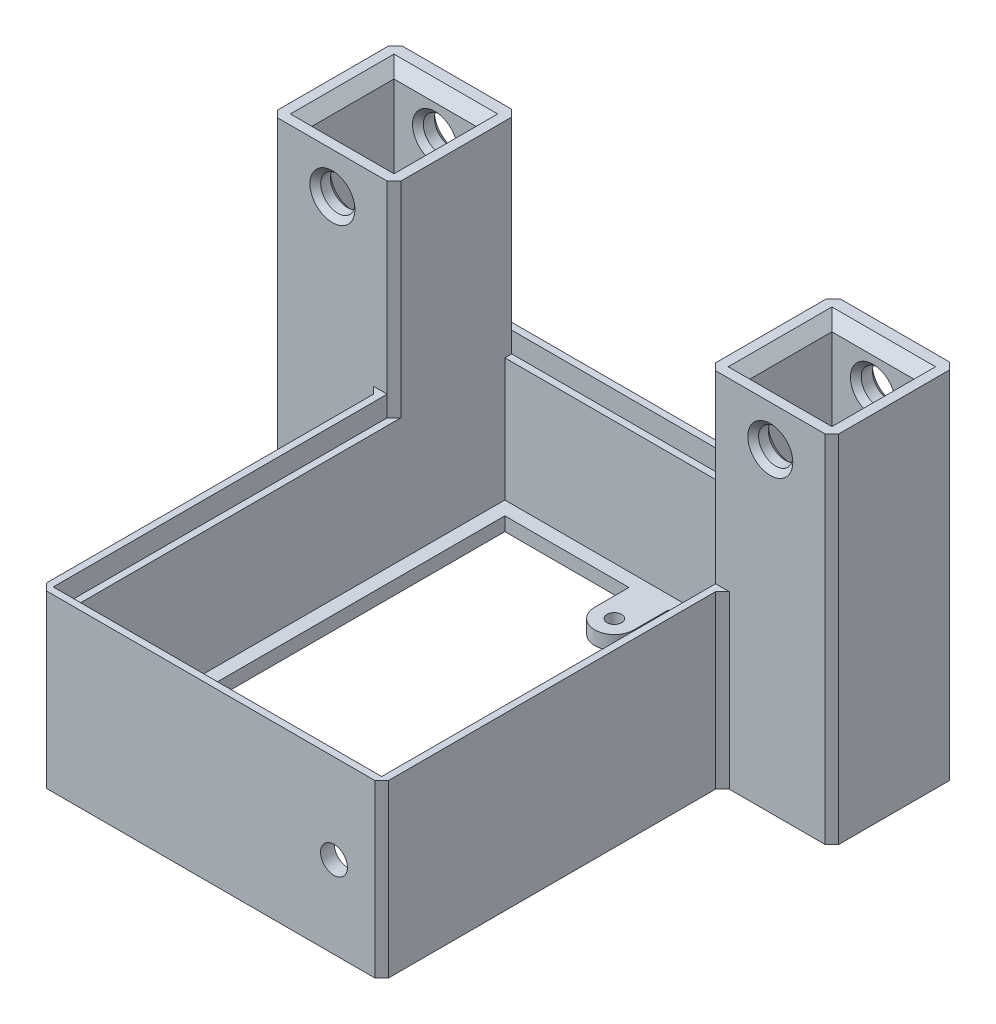
SolidWorks part; units mm, degrees
ref_plane "Front Plane" through (0, 0, 0) normal (0, 0, 1) x (1, 0, 0)
ref_plane "Top Plane" through (0, 0, 0) normal (0, 1, 0) x (1, 0, 0)
ref_plane "Right Plane" through (0, 0, 0) normal (1, 0, 0) x (0, 0, -1)
sketch "Sketch3" plane through (0, 0, 0) normal (0, 1, 0) x (-1, 0, 0)
  line L1 (0, 0) -> (63.5, 0)
  line L2 (0, 0) -> (0, 86.36)
  line L3 (0, 86.36) -> (63.5, 86.36)
  line L4 (63.5, 0) -> (63.5, 86.36)
  dimension "D1" = 86.36
  dimension "D2" = 63.5
extrude "Boss-Extrude2" add sketch "Sketch3" against normal blind 31.75
sketch "Sketch4" plane through (0, -31.75, 0) normal (0, -1, 0) x (1, 0, 0)
  line L1 (-2.54, 83.82) -> (-60.96, 83.82)
  line L2 (-2.54, 83.82) -> (-2.54, 2.54)
  line L3 (-2.54, 2.54) -> (-60.96, 2.54)
  line L4 (-60.96, 83.82) -> (-60.96, 2.54)
  line L8 (-63.5, 86.36) -> (0, 86.36) construction
  line L9 (0, 0) -> (-63.5, 0) construction
  line L10 (0, 86.36) -> (0, 0) construction
  line L11 (-63.5, 0) -> (-63.5, 86.36) construction
  dimension "D1" = 2.54
  dimension "D2" = 2.54
  dimension "D3" = 2.54
  dimension "D4" = 2.54
extrude "Cut-Extrude2" cut sketch "Sketch4" against normal offset from surface (27.94 mm away) 3.81 up to face at (-31.75, 0, 43.18)
sketch "Sketch5" plane through (-63.5, 0, 0) normal (1, 0, 0) x (0, 0, -1)
  line L0 (-86.36, -31.75) -> (-86.36, 0) construction
  line L5 (0, -31.75) -> (-86.36, -31.75) construction
  circle A0 centre (-76.327, -19.177) radius 5.715
  dimension "D1" = 11.43
  dimension "D2" = 6.858
  dimension "D3" = 4.318
extrude "Power Jack Hole" cut sketch "Sketch5" along normal up to next
sketch "Sketch6" plane through (-63.5, 0, 0) normal (-1, 0, 0) x (0, 0, 1)
  line L0 (46.54, 0) -> (46.54, 36.83)
  line L1 (46.54, 36.83) -> (0, 36.83)
  line L2 (0, 36.83) -> (0, 34.29)
  line L3 (0, 34.29) -> (44, 34.29)
  line L4 (44, 34.29) -> (44, 0)
  line L5 (0, 0) -> (86.36, 0) construction
  line L6 (44, 0) -> (46.54, 0)
  line L7 (0, -31.75) -> (0, 0) construction
  dimension "D1" = 44
  dimension "D2" = 34.29
  dimension "D3" = 2.54
  dimension "D4" = 2.54
extrude "Motor Mounting Shape" add sketch "Sketch6" against normal up to surface (63.5 mm away) up to face at (0, -15.875, 43.18)
sketch "Sketch8" plane through (0, 36.83, 0) normal (0, 1, 0) x (1, 0, 0)
  line L0 (-47.25, -38.77) -> (-16.25, -7.77) construction
  line L1 (-16.25, -38.77) -> (-47.25, -7.77) construction
  line L2 (-47.25, -38.77) -> (-47.25, -7.77) construction
  line L3 (-47.25, -7.77) -> (-16.25, -7.77) construction
  line L4 (-31.75, -46.54) -> (-31.75, 0) construction
  line L5 (0, -46.54) -> (-63.5, -46.54) construction
  line L6 (0, 0) -> (-63.5, 0) construction
  line L7 (-40.64, 0) -> (-22.86, 0)
  line L8 (-22.86, 0) -> (-22.86, -23.27)
  line L9 (-40.64, -23.27) -> (-40.64, 0)
  circle A1 centre (-47.25, -7.77) radius 1.6
  circle A2 centre (-16.25, -7.77) radius 1.6
  circle A3 centre (-16.25, -38.77) radius 1.6
  circle A4 centre (-47.25, -38.77) radius 1.6
  arc A6 (-40.64, -23.27) -> (-22.86, -23.27) centre (-31.75, -23.27) ccw
  point P10 (-31.75, -23.27)
  dimension "D2" = 3.2
  dimension "D3" = 8.89
  dimension "D1" = 31
extrude "Motor-Mounting-Holes" cut sketch "Sketch8" against normal up to next
sketch "Sketch13" plane through (0, 0, 0) normal (0, 1, 0) x (1, 0, 0)
  line L0 (-31.75, -85.09) -> (-31.75, -86.36) construction
  line L1 (-62.23, -1.27) -> (-1.27, -1.27)
  line L2 (-62.23, -1.27) -> (-62.23, -85.09)
  line L3 (-62.23, -85.09) -> (-1.27, -85.09)
  line L4 (-1.27, -1.27) -> (-1.27, -85.09)
  line L5 (-63.5, -86.36) -> (0, -86.36) construction
  line L6 (-63.5, -46.54) -> (-63.5, -86.36) construction
  line L7 (0, 0) -> (-63.5, 0) construction
  dimension "D1" = 1.27
  dimension "D2" = 1.27
  dimension "D3" = 1.27
extrude "Cut-Extrude7" cut sketch "Sketch13" against normal up to surface (3.81 mm away) up to face at (-31.75, -3.81, 43.18)
sketch "Sketch9" plane through (0, -31.75, 0) normal (0, -1, 0) x (1, 0, 0)
  line L0 (1.27, 23.114) -> (-2.54, 23.114)
  line L1 (1.27, 0) -> (20.32, 0)
  line L2 (1.27, 4.064) -> (1.27, 19.304)
  line L3 (1.27, 23.114) -> (20.32, 23.114)
  line L5 (20.32, 23.114) -> (20.32, 0)
  line L6 (1.27, 19.304) -> (16.51, 19.304)
  line L7 (16.51, 19.304) -> (16.51, 4.064)
  line L8 (16.51, 4.064) -> (1.27, 4.064)
  line L10 (-2.54, 23.114) -> (-2.54, 0)
  line L11 (-31.75, 86.36) -> (-31.75, 0) construction
  line L12 (-2.54, 0) -> (1.27, 0)
  line L13 (1.27, 19.304) -> (1.27, 4.064)
  line L14 (0, 0) -> (-63.5, 0) construction
  line L15 (-63.5, 86.36) -> (0, 86.36) construction
  line L16 (-80.01, 19.304) -> (-80.01, 4.064)
  line L17 (-80.01, 4.064) -> (-64.77, 4.064)
  line L18 (-64.77, 4.064) -> (-64.77, 19.304)
  line L19 (-64.77, 19.304) -> (-80.01, 19.304)
  line L20 (-60.96, 0) -> (-64.77, 0)
  line L21 (-60.96, 23.114) -> (-60.96, 0)
  line L22 (-64.77, 23.114) -> (-60.96, 23.114)
  line L23 (-64.77, 23.114) -> (-83.82, 23.114)
  line L24 (-83.82, 23.114) -> (-83.82, 0)
  line L25 (-64.77, 0) -> (-83.82, 0)
  line L26 (-2.54, 2.54) -> (-2.54, 83.82) construction
  dimension "D1" = 3.81
  dimension "D2" = 4.064
  dimension "D3" = 3.81
  dimension "D4" = 15.24
  dimension "D5" = 3.81
  dimension "D6" = 3.81
  dimension "D8" = 33.02
extrude "Boss-Extrude3" add sketch "Sketch9" against normal blind 66 contours L1 L5 L3 L0 L10 L12 | L13 L8 L7 L6 | L20 L25 L24 L23 L22 L21 | L16 L17 L18 L19
chamfer "Chamfer1" distance 2 angle 45 8 edges at (-64.77, 34.25, 11.684) (-72.39, 34.25, 4.064) (-80.01, 34.25, 11.684) (-72.39, 34.25, 19.304) (8.89, 34.25, 4.064) (1.27, 34.25, 11.684) (16.51, 34.25, 11.684) (8.89, 34.25, 19.304)
sketch "Sketch11" plane through (0, 0, 0) normal (1, 0, 0) x (0, 0, -1)
  line L0 (-44, 0) -> (-44, 34.29)
  line L1 (-44, 34.29) -> (0, 34.29)
  line L2 (0, 34.29) -> (0, 36.83)
  line L3 (0, 36.83) -> (-86.36, 36.83)
  line L4 (-86.36, 36.83) -> (-86.36, 0)
  line L5 (-86.36, 0) -> (-44, 0)
  line L6 (-46.54, 36.83) -> (0, 36.83) construction
  point P9 (-86.36, 0)
  point P12 (0, 36.83)
extrude "Cut-Extrude5" cut sketch "Sketch11" against normal through all
sketch "Sketch12" plane through (0, 0, 23.114) normal (0, 0, 1) x (1, 0, 0)
  line L0 (20.32, -31.75) -> (0, -31.75) construction
  line L1 (-60.96, 34.25) -> (-60.96, -3.81) construction
  line L2 (-2.54, 34.25) -> (-2.54, -3.81) construction
  circle A0 centre (8.89, 26.67) radius 3.175
  circle A1 centre (-72.39, 26.67) radius 3.175
  dimension "D1" = 6.35
  dimension "D3" = 6.35
  dimension "D2" = 58.42
  dimension "D4" = 11.43
  dimension "D5" = 11.43
extrude "Leg Holes" cut sketch "Sketch12" against normal through all
chamfer "Chamfer2" distance 1 angle 45 8 edges at (12.065, 26.67, 23.114) (5.715, 26.67, 19.304) (12.065, 26.67, 4.064) (12.065, 26.67, 0) (-69.215, 26.67, 0) (-75.565, 26.67, 4.064) (-69.215, 26.67, 19.304) (-69.215, 26.67, 23.114)
sketch "Sketch14" plane through (0, -31.75, 0) normal (0, -1, 0) x (1, 0, 0)
  line L1 (-58.42, 81.28) -> (-5.08, 81.28)
  line L2 (-58.42, 81.28) -> (-58.42, 5.08)
  line L3 (-58.42, 5.08) -> (-5.08, 5.08)
  line L4 (-5.08, 81.28) -> (-5.08, 5.08)
  line L5 (-2.54, 83.82) -> (-60.96, 83.82) construction
  line L7 (-2.54, 2.54) -> (-2.54, 83.82) construction
  line L10 (-60.96, 83.82) -> (-2.54, 83.82)
  line L11 (-60.96, 83.82) -> (-60.96, 2.54)
  line L12 (-60.96, 2.54) -> (-2.54, 2.54)
  line L13 (-2.54, 83.82) -> (-2.54, 2.54)
  dimension "D1" = 2.54
  dimension "D2" = 2.54
  dimension "D3" = 2.54
  dimension "D4" = 2.54
extrude "Boss-Extrude5" add sketch "Sketch14" along normal blind 2.54 from offset 5.08 offset against normal yes
sketch "Sketch15" plane through (0, 0, 86.36) normal (0, 0, 1) x (1, 0, 0)
  line L0 (-63.5, -31.75) -> (0, -31.75) construction
  line L1 (0, -31.75) -> (0, 0) construction
  circle A0 centre (-8.85, -16.55) radius 2.5
  dimension "D1" = 5
  dimension "D2" = 12.7
  dimension "D3" = 6.35
extrude "Cut-Extrude8" cut sketch "Sketch15" against normal up to next
chamfer "Chamfer3" distance 1.27 angle 45 12 edges at (-63.5, -15.875, 86.36) (0, -15.875, 86.36) (0, -15.875, 23.114) (20.32, 1.25, 23.114) (20.32, 1.25, 0) (-2.54, 15.22, 23.114) (-2.54, 17.125, 0) (-60.96, 15.22, 23.114) (-60.96, 17.125, 0) (-83.82, 1.25, 0) (-83.82, 1.25, 23.114) (-63.5, -15.875, 23.114)
sketch "Sketch16" plane through (0, -29.21, 0) normal (0, -1, 0) x (1, 0, 0)
  line L0 (-35.386, 2.54) -> (-28.114, 2.54)
  line L1 (-60.96, 2.54) -> (-2.54, 2.54) construction
  line L2 (-28.114, 2.54) -> (-28.114, 11.43)
  line L3 (-35.386, 11.43) -> (-35.386, 2.54)
  line L4 (-60.96, 43.18) -> (-5.08, 43.18) construction
  line L5 (-60.96, 83.82) -> (-60.96, 2.54) construction
  line L6 (-5.08, 5.08) -> (-5.08, 81.28) construction
  line L7 (-58.42, 5.08) -> (-5.08, 5.08) construction
  line L8 (-35.386, 74.93) -> (-35.386, 83.82)
  line L9 (-35.386, 83.82) -> (-28.114, 83.82)
  line L10 (-28.114, 83.82) -> (-28.114, 74.93)
  arc A0 (-28.114, 11.43) -> (-35.386, 11.43) centre (-31.75, 11.43) ccw
  circle A1 centre (-31.75, 11.43) radius 1.35
  circle A2 centre (-31.75, 74.93) radius 1.35
  arc A3 (-28.114, 74.93) -> (-35.386, 74.93) centre (-31.75, 74.93) cw
  point P16 (-31.75, 2.54)
  point P17 (-31.75, 2.54)
  point P23 (-31.75, 83.82)
  dimension "D1" = 2.7
  dimension "D2" = 2.286
  dimension "D3" = 6.35
extrude "Boss-Extrude6" add sketch "Sketch16" against normal up to surface (2.54 mm away) up to face at (-31.75, -26.67, 43.18)
